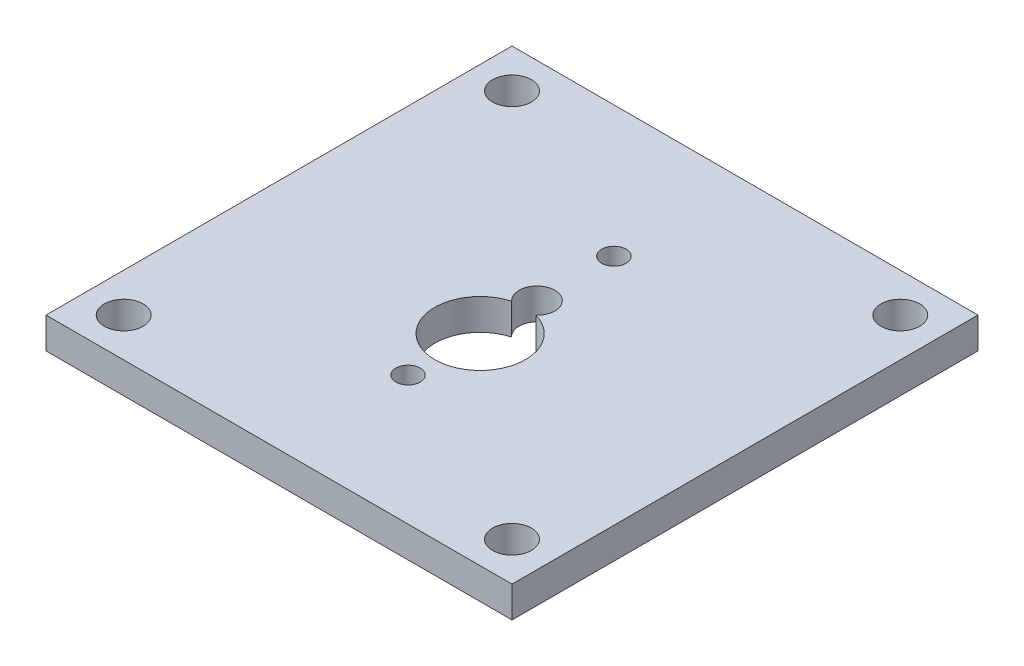
SolidWorks part; units mm, degrees
ref_plane "Front Plane" through (0, 0, 0) normal (0, 0, 1) x (1, 0, 0)
ref_plane "Top Plane" through (0, 0, 0) normal (0, 1, 0) x (1, 0, 0)
ref_plane "Right Plane" through (0, 0, 0) normal (1, 0, 0) x (0, 0, -1)
sketch "Sketch1" plane through (0, 0, 0) normal (0, 1, 0) x (1, 0, 0)
  line L0 (-30, 25) -> (30, 25) construction
  line L1 (-30, -30) -> (30, -30)
  line L2 (-30, -30) -> (-30, 30)
  line L3 (-30, 30) -> (30, 30)
  line L4 (30, -30) -> (30, 30)
  line L5 (-30, -30) -> (30, 30) construction
  line L6 (-30, 30) -> (30, -30) construction
  line L7 (-25, 30) -> (-25, -30) construction
  line L8 (-25, 0) -> (-4.1533, 0) construction
  circle A0 centre (-25, 25) radius 2.5
  circle A1 centre (25, 25) radius 2.5
  circle A2 centre (25, -25) radius 2.5
  circle A3 centre (-25, -25) radius 2.5
  arc A4 (-1.5654, 1.5213) -> (1.5654, 1.5213) centre (0, -4.1033) ccw
  arc A5 (1.5654, 1.5213) -> (-1.5654, 1.5213) centre (0, 3.2171) ccw
  circle A6 centre (0, -13.3839) radius 1.5654
  circle A7 centre (0, 13.1255) radius 1.5748
  point P0 (0, 0)
  point P26 (0, 0)
  dimension "D5" = 2
  dimension "D1" = 60
  dimension "D2" = 60
  dimension "D3" = 5
  dimension "D4" = 5
extrude "Boss-Extrude3" add sketch "Sketch1" along normal blind 4 contours A4 A5 | L2 L1 L4 L3 | A7 | A0 | A3 | A6 | A2 | A1 region at (0, 0, 3.1787)
